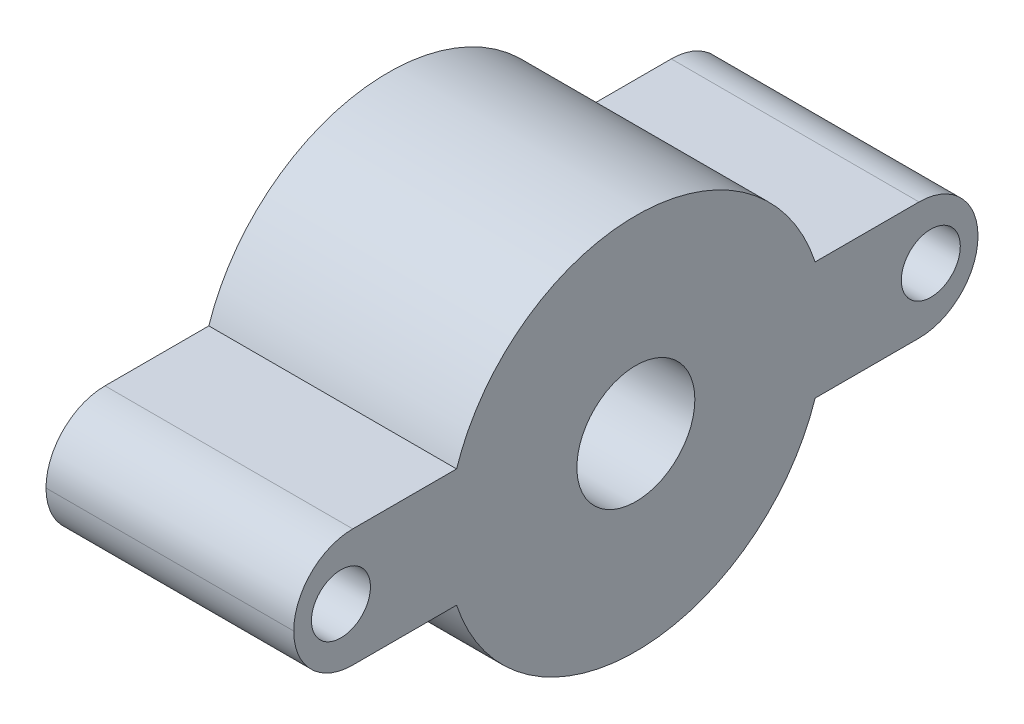
SolidWorks part; units mm, degrees
ref_plane "Front Plane" through (0, 0, 0) normal (0, 0, 1) x (1, 0, 0)
ref_plane "Top Plane" through (0, 0, 0) normal (0, 1, 0) x (1, 0, 0)
ref_plane "Right Plane" through (0, 0, 0) normal (1, 0, 0) x (0, 0, -1)
sketch "Sketch1" plane through (0, 0, 0) normal (1, 0, 0) x (0, 0, -1)
  line L1 (0, 0) -> (70, 0)
  line L2 (0, 0) -> (0, 10)
  line L3 (0, 10) -> (70, 10)
  line L4 (70, 0) -> (70, 10)
  dimension "D1" = 10
  dimension "D2" = 70
extrude "Boss-Extrude1" add sketch "Sketch1" along normal blind 5
sketch "Sketch2" plane through (5, 0, 0) normal (1, 0, 0) x (0, 0, -1)
  circle A0 centre (35, 5) radius 16
  dimension "D1" = 32
extrude "Boss-Extrude2" add sketch "Sketch2" against normal blind 5 and the other way blind 16
sketch "Sketch3" plane through (5, 0, 0) normal (1, 0, 0) x (0, 0, -1)
  line L1 (0, 10) -> (70, 10)
  line L2 (0, 10) -> (0, 0)
  line L3 (0, 0) -> (70, 0)
  line L4 (70, 10) -> (70, 0)
extrude "Boss-Extrude3" add sketch "Sketch3" along normal blind 16
sketch "Sketch4" plane through (21, 0, 0) normal (1, 0, 0) x (0, 0, -1)
  circle A0 centre (10, 5) radius 2.5
  circle A1 centre (60, 5) radius 2.5
  arc A2 (50.1987, 10) -> (19.8013, 10) centre (35, 5) ccw construction
  point P7 (35, 21)
  dimension "D3" = 5
  dimension "D4" = 5
  dimension "D1" = 25
  dimension "D2" = 25
extrude "Cut-Extrude1" cut sketch "Sketch4" against normal blind 11
sketch "Sketch5" plane through (21, 0, 0) normal (1, 0, 0) x (0, 0, -1)
  circle A0 centre (10, 5) radius 1.5
  circle A1 centre (60, 5) radius 1.5
  dimension "D1" = 3
  dimension "D2" = 3
extrude "Cut-Extrude2" cut sketch "Sketch5" against normal blind 38
sketch "Sketch6" plane through (0, 0, 0) normal (-1, 0, 0) x (0, 0, 1)
  circle A0 centre (-35, 5) radius 12
  dimension "D1" = 24
extrude "Cut-Extrude3" cut sketch "Sketch6" against normal blind 11
sketch "Sketch7" plane through (21, 0, 0) normal (1, 0, 0) x (0, 0, -1)
  circle A0 centre (35, 5) radius 5
  dimension "D1" = 10
extrude "Cut-Extrude4" cut sketch "Sketch7" against normal blind 40
sketch "Sketch8" plane through (0, 0, 0) normal (-1, 0, 0) x (0, 0, 1)
  line L0 (-50.1987, 0) -> (-70, 0) construction
  line L1 (-70, 10) -> (-64, 10)
  line L2 (-70, 10) -> (-70, 0)
  line L3 (-70, 0) -> (-64, 0)
  line L4 (-64, 10) -> (-64, 0)
  line L5 (0, 0) -> (-19.8013, 0) construction
  line L6 (0, 10) -> (-6, 10)
  line L7 (0, 10) -> (0, 0)
  line L8 (0, 0) -> (-6, 0)
  line L9 (-6, 10) -> (-6, 0)
  point P14 (-3, 10)
  dimension "D1" = 6
  dimension "D2" = 3
extrude "Cut-Extrude5" cut sketch "Sketch8" against normal blind 40
fillet "Fillet1" radius 5 1 edges at (10.5, 10, -64) type face fillet first side face at (10.5, 10, -57.0993) second side face at (10.5, 5, -64)
fillet "Fillet2" radius 5 1 edges at (10.5, 10, -6) type face fillet first side face at (10.5, 10, -12.9007) second side face at (10.5, 5, -6)
fillet "Fillet3" radius 5 1 edges at (10.5, 0, -6) type face fillet first side face at (10.5, 2.5, -6) second side face at (10.5, 0, -12.9007)
fillet "Fillet4" radius 5 1 edges at (10.5, 0, -64) type face fillet first side face at (10.5, 0, -57.0993) second side face at (10.5, 2.5, -64)
